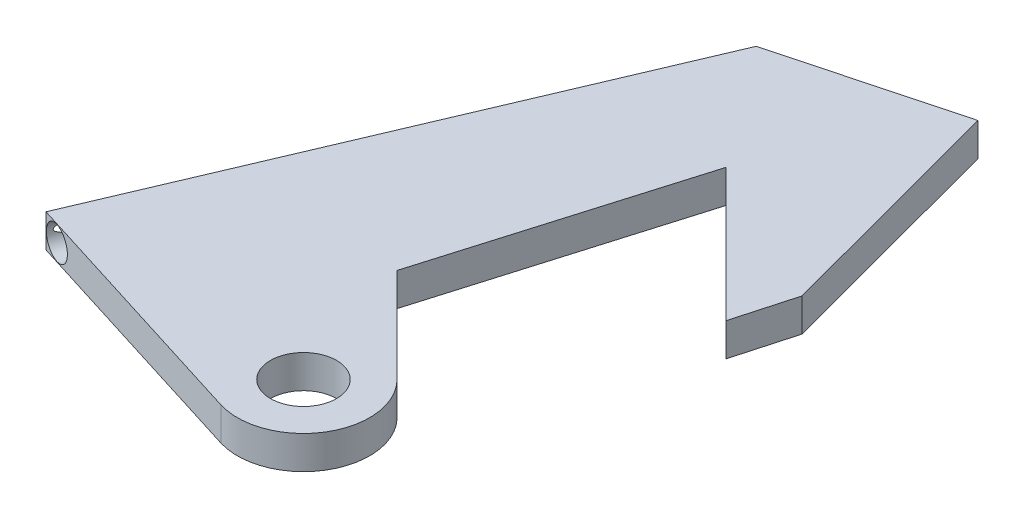
SolidWorks part; units mm, degrees
ref_plane "Front Plane" through (0, 0, 0) normal (0, 0, 1) x (1, 0, 0)
ref_plane "Top Plane" through (0, 0, 0) normal (0, 1, 0) x (1, 0, 0)
ref_plane "Right Plane" through (0, 0, 0) normal (1, 0, 0) x (0, 0, -1)
sketch "Sketch1" plane through (0, 0, 0) normal (0, 1, 0) x (1, 0, 0)
  line L8 (6.6803, 23.8046) -> (-18.5409, 17.0908)
  line L9 (-18.5409, 17.0908) -> (-49.0366, -54.6767)
  line L12 (13.498, -19.3113) -> (15.8795, -10.7537)
  line L14 (-2.7155, -50.4526) -> (-16.4492, -36.7162)
  line L15 (-0.2503, -64.2218) -> (8.9811, -34.0664) construction
  line L16 (-33.45, -172.6721) -> (154.2855, 440.5857) construction
  line L17 (-1.4647, -63.85) -> (7.7667, -33.6946) construction
  line L18 (-10.7741, -61.0002) -> (-1.5427, -30.8448) construction
  line L19 (-49.0366, -54.6767) -> (-12.3816, -66.1571)
  line L20 (-5.6282, -0.1851) -> (-16.4492, -36.7162)
  line L21 (13.498, -19.3113) -> (-5.6282, -0.1851)
  line L22 (15.8795, -10.7537) -> (6.6803, 23.8046)
  line L23 (-33.6661, -172.5997) -> (154.0693, 440.6582) construction
  circle A4 centre (-9.5834, -57.0524) radius 4.7625
  arc A5 (-12.3816, -66.1571) -> (-2.7155, -50.4526) centre (-9.5834, -57.0524) ccw
  point P2 (0, 0)
  dimension "D2" = 38.1
  dimension "D1" = 1.27
  dimension "D3" = 77.978
  dimension "D4" = 35.7617
extrude "Boss-Extrude1" add sketch "Sketch1" along normal blind 4.7625
sketch "Sketch2" plane through (-19.9756, 0, 63.7787) normal (-0.2989, 0, 0.9543) x (0.9543, 0, 0.2989)
  line L0 (-30.4531, 2.3813) -> (-28.0638, 2.3813) construction
  line L1 (-30.4531, 4.7625) -> (-30.4531, 0) construction
hole_wizard "#14 (0.182) Diameter Hole1" positions "Sketch3" profile "Sketch4" hole size "#14" standard "ANSI Inch"
sketch "Sketch3" plane through (-19.9756, 0, 63.7787) normal (-0.2989, 0, 0.9543) x (0.9543, 0, 0.2989)
  point P0 (-28.0638, 2.3813)
sketch "Sketch4" plane through (-46.7565, 2.3813, 55.3908) normal (0, 1, 0) x (0.9543, 0, 0.2989)
  line L0 (0, 0) -> (0, 3.9288)
  line L1 (0, 3.9288) -> (2.3114, 2.54)
  line L2 (2.3114, 2.54) -> (2.3114, 0)
  line L5 (2.3114, 0) -> (0, 0)
  line L10 (0, 3.9288) -> (-2.3114, 2.54) construction
  line L11 (0, -6.35) -> (0, 107.95) construction
  dimension "Hole Dia." = 4.6228
  dimension "Hole Depth" = 2.54
  dimension "Drill Angle" = 118
